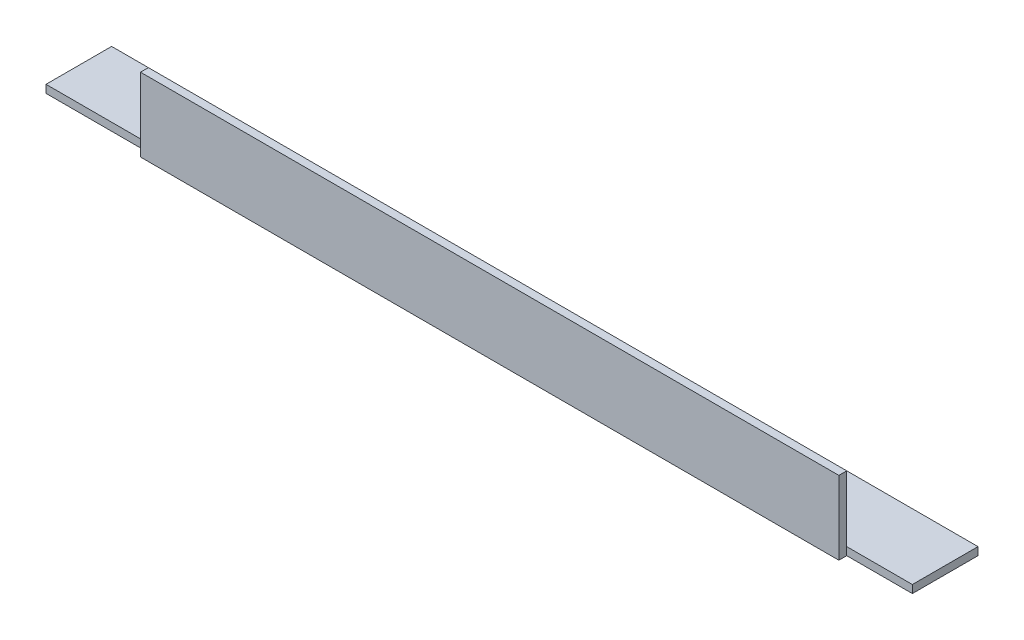
SolidWorks part; units mm, degrees
ref_plane "Спереди" through (0, 0, 0) normal (0, 0, 1) x (1, 0, 0)
ref_plane "Сверху" through (0, 0, 0) normal (0, 1, 0) x (1, 0, 0)
ref_plane "Справа" through (0, 0, 0) normal (1, 0, 0) x (0, 0, -1)
sketch "Эскиз1" plane through (0, 0, 0) normal (1, 0, 0) x (0, 0, -1)
  line L0 (0, 25) -> (0, 0)
  line L1 (0, 0) -> (25, 0)
extrude "Вытянуть-Тонкостенный1" add sketch "Эскиз1" along normal blind 330 thin thin type one direction wall 3
sketch "Эскиз2" plane through (0, -3, 0) normal (0, -1, 0) x (1, 0, 0)
  line L0 (330, 3) -> (330, -25) construction
  line L1 (0, 3) -> (39, 3)
  line L2 (0, 3) -> (0, 0)
  line L3 (0, 0) -> (39, 0)
  line L4 (39, 3) -> (39, 0)
  line L5 (330, 3) -> (305, 3)
  line L6 (330, 3) -> (330, 0)
  line L7 (330, 0) -> (305, 0)
  line L8 (305, 3) -> (305, 0)
  line L9 (330, 3) -> (0, 3) construction
extrude "Вырез-Вытянуть1" cut sketch "Эскиз2" against normal through all
